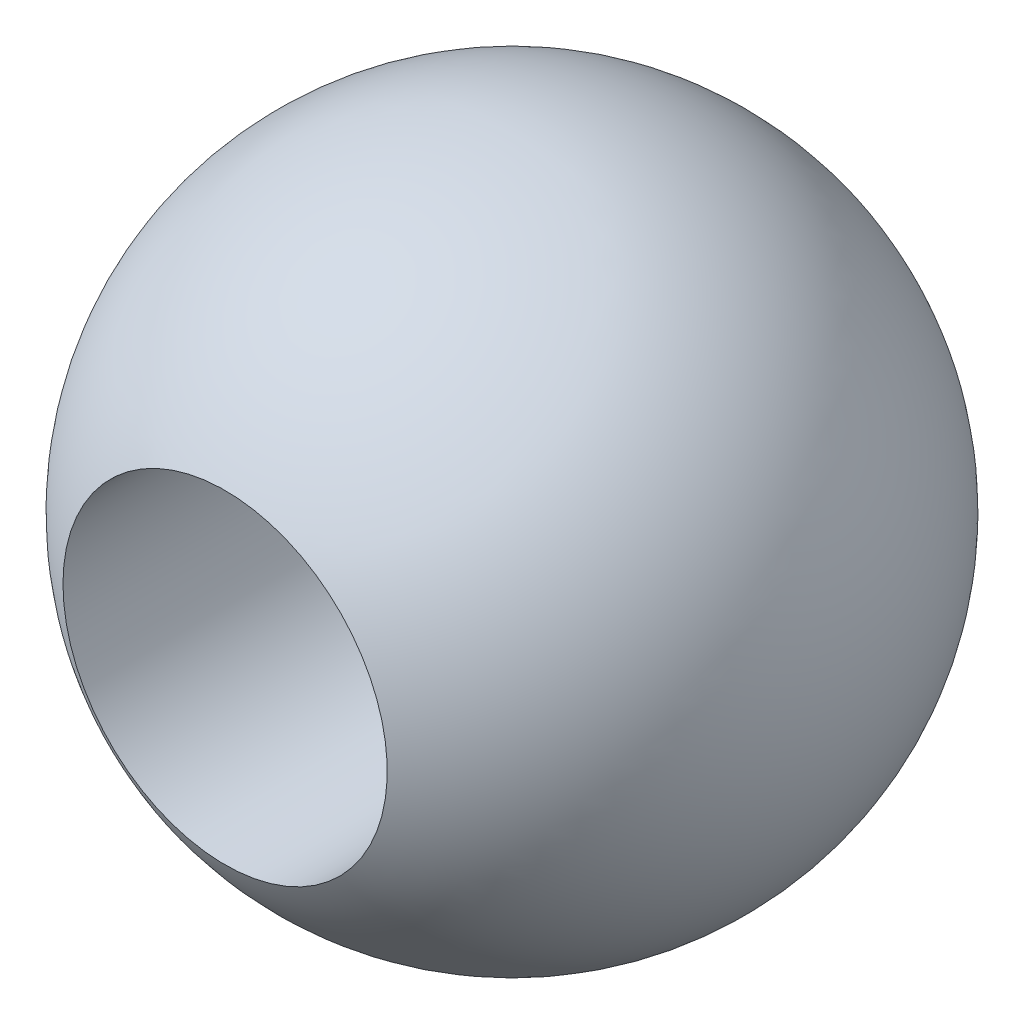
SolidWorks part; units mm, degrees
ref_plane "Front Plane" through (0, 0, 0) normal (0, 0, 1) x (1, 0, 0)
ref_plane "Top Plane" through (0, 0, 0) normal (0, 1, 0) x (1, 0, 0)
ref_plane "Right Plane" through (0, 0, 0) normal (1, 0, 0) x (0, 0, -1)
sketch "Sketch1" plane through (0, 0, 0) normal (0, 0, 1) x (1, 0, 0)
  line L0 (0, 0) -> (0, -6.6403) construction
  line L1 (0, 3.15) -> (0, -3.15)
  arc A0 (0, -3.15) -> (0, 3.15) centre (0, 0) ccw
  dimension "D1" = 6.3
revolve "Revolve1" add sketch "Sketch1" angle 360 about L0
sketch "Sketch2" plane through (0, 0, 0) normal (0, 0, 1) x (1, 0, 0)
  circle A0 centre (0, 0) radius 1.55
  dimension "D1" = 3.1
extrude "Cut-Extrude1" cut sketch "Sketch2" against normal blind 10 and the other way blind 10
